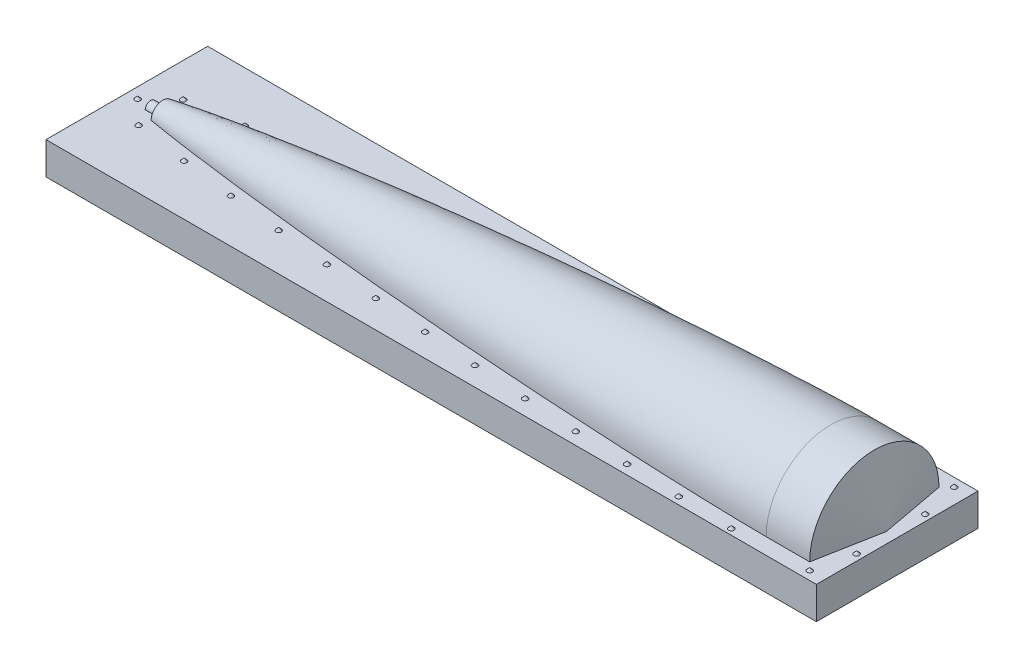
SolidWorks part; units mm, degrees
ref_plane "Front Plane" through (0, 0, 0) normal (0, 0, 1) x (1, 0, 0)
ref_plane "Top Plane" through (0, 0, 0) normal (0, 1, 0) x (1, 0, 0)
ref_plane "Right Plane" through (0, 0, 0) normal (1, 0, 0) x (0, 0, -1)
sketch "Sketch4" plane through (0, 0, 0) normal (0, 1, 0) x (1, 0, 0)
  line L0 (838.2216, 76.204) -> (889.568, 76.204)
  line L1 (889.568, 76.204) -> (903.7797, 0)
  line L2 (0, 0) -> (903.7797, 0) construction
  line L3 (49.2388, 6.35) -> (36.5388, 6.35)
  line L4 (49.2388, 6.35) -> (50.8212, 13.6952)
  line L5 (36.5388, 6.35) -> (33.9086, 0)
  line L6 (33.9086, 0) -> (903.7797, 0)
  spline S0 degree 4 poles (0.4116, 2.1681) (0.5035, 2.2183) (0.6887, 2.3156) (1.002, 2.4664) (1.4785, 2.6758) (2.1113, 2.9321) (3.0416, 3.2792) (4.4759, 3.768) (6.7944, 4.485) (9.7489, 5.3043) (13.1672, 6.1761) (17.4494, 7.1922) (22.1004, 8.2295) (27.2517, 9.3071) (32.654, 10.3833) (38.124, 11.4218) (42.9515, 12.3115) (49.1089, 13.4036) (53.3744, 14.1376) (58.7785, 15.0476) (63.6012, 15.8365) (68.9441, 16.698) (76.5361, 17.8884) (86.8586, 19.455) (98.7324, 21.1846) (110.6839, 22.8577) (120.8839, 24.2402) (131.1653, 25.6027) (141.4841, 26.9388) (153.5711, 28.4629) (167.4123, 30.1559) (181.2629, 31.8024) (195.1165, 33.4051) (212.4407, 35.3579) (229.7712, 37.247) (247.1084, 39.0777) (264.451, 40.854) (278.3284, 42.2438) (295.6787, 43.9433) (316.5048, 45.9247) (340.8095, 48.1557) (368.5956, 50.6005) (396.3905, 52.9447) (424.1933, 55.1916) (452.0037, 57.3435) (479.8212, 59.4019) (507.6453, 61.3674) (535.4759, 63.2399) (570.2718, 65.4634) (612.0388, 67.9402) (660.7836, 70.5395) (709.5475, 72.7531) (747.8743, 74.1952) (775.7546, 75.0554) (794.4539, 75.5468) (808.5625, 75.8548) (821.5655, 76.0752) (831.0831, 76.1755) (835.8421, 76.204) (838.2216, 76.204) knots 0 0 0 0 0 0.000497 0.000994 0.00165 0.002474 0.003736 0.005714 0.008837 0.014015 0.018266 0.022517 0.029658 0.0368 0.042975 0.04915 0.055325 0.061501 0.06978 0.07392 0.07806 0.08634 0.09462 0.110946 0.127272 0.143598 0.151761 0.159924 0.176484 0.193044 0.209604 0.226164 0.242723 0.259283 0.292403 0.308963 0.325522 0.342082 0.358642 0.391762 0.424881 0.458001 0.49112 0.52424 0.557359 0.590479 0.623599 0.656718 0.689838 0.756077 0.822316 0.888555 0.921675 0.938235 0.954794 0.977397 0.988699 1 1 1 1 1 construction
  spline S1 degree 4 poles (50.8212, 13.6952) (52.4334, 13.9739) (54.8422, 14.3848) (58.7785, 15.0476) (63.6012, 15.8365) (68.9441, 16.698) (76.5361, 17.8884) (86.8586, 19.455) (98.7324, 21.1846) (110.6839, 22.8577) (120.8839, 24.2402) (131.1653, 25.6027) (141.4841, 26.9388) (153.5711, 28.4629) (167.4123, 30.1559) (181.2629, 31.8024) (195.1165, 33.4051) (212.4407, 35.3579) (229.7712, 37.247) (247.1084, 39.0777) (264.451, 40.854) (278.3284, 42.2438) (295.6787, 43.9433) (316.5048, 45.9247) (340.8095, 48.1557) (368.5956, 50.6005) (396.3905, 52.9447) (424.1933, 55.1916) (452.0037, 57.3435) (479.8212, 59.4019) (507.6453, 61.3674) (535.4759, 63.2399) (570.2718, 65.4634) (612.0388, 67.9402) (660.7836, 70.5395) (709.5475, 72.7531) (747.8743, 74.1952) (775.7546, 75.0554) (794.4539, 75.5468) (808.5625, 75.8548) (821.5655, 76.0752) (831.0831, 76.1755) (835.8421, 76.204) (838.2216, 76.204) knots 0.061501 0.061501 0.061501 0.061501 0.061501 0.06978 0.07392 0.07806 0.08634 0.09462 0.110946 0.127272 0.143598 0.151761 0.159924 0.176484 0.193044 0.209604 0.226164 0.242723 0.259283 0.292403 0.308963 0.325522 0.342082 0.358642 0.391762 0.424881 0.458001 0.49112 0.52424 0.557359 0.590479 0.623599 0.656718 0.689838 0.756077 0.822316 0.888555 0.921675 0.938235 0.954794 0.977397 0.988699 1 1 1 1 1
  point P6 (0, 0)
  dimension "D1" = 869.8712
  dimension "D2" = 12.7
  dimension "D3" = 102.157
  dimension "D4" = 79.436
  dimension "D5" = 51.3464
  dimension "D6" = 76.204
revolve "Revolve1" add sketch "Sketch4" angle 180 about L2
sketch "Sketch5" plane through (0, 0, 0) normal (0, -1, 0) x (1, 0, 0)
  line L0 (8.5086, 95.254) -> (8.5086, -95.254)
  line L1 (889.568, -76.204) -> (838.2216, -76.204) construction
  line L2 (889.568, 76.204) -> (838.2216, 76.204) construction
  line L3 (8.5086, -95.254) -> (916.4797, -95.254)
  line L6 (8.5086, 95.254) -> (916.4797, 95.254)
  line L7 (916.4797, 95.254) -> (916.4797, -95.254)
  dimension "D1" = 12.7
  dimension "D2" = 19.05
  dimension "D3" = 19.05
  dimension "D4" = 25.4
extrude "Boss-Extrude1" add sketch "Sketch5" along normal blind 38.1
sketch "Sketch8" plane through (0, 0, 0) normal (0, 1, 0) x (1, 0, 0)
  line L0 (50.8212, -13.6952) -> (48.6578, -26.2096) construction
  line L1 (176.6029, -31.2441) -> (175.1098, -43.856) construction
  line L2 (302.896, -44.6243) -> (301.6912, -57.267) construction
  line L3 (429.4223, -55.5836) -> (428.429, -68.2447) construction
  line L4 (556.1056, -64.5474) -> (555.3063, -77.2222) construction
  line L5 (682.915, -71.5029) -> (682.3308, -84.1895) construction
  line L6 (809.8401, -75.8636) -> (809.5993, -88.5614) construction
  line L7 (896.6738, -38.102) -> (909.1586, -40.4303) construction
  line L8 (903.7797, 0) -> (889.568, -76.204) construction
  line L9 (889.568, -76.204) -> (898.5482, -85.1842) construction
  line L10 (889.568, -76.204) -> (838.2216, -76.204) construction
  line L11 (33.9086, 0) -> (21.2086, 0) construction
  line L12 (889.568, 76.204) -> (898.5482, 85.1842) construction
  line L13 (896.6738, 38.102) -> (909.1586, 40.4303) construction
  line L14 (809.8401, 75.8636) -> (809.5993, 88.5614) construction
  line L15 (682.915, 71.5029) -> (682.3308, 84.1895) construction
  line L16 (556.1056, 64.5474) -> (555.3063, 77.2222) construction
  line L17 (429.4223, 55.5836) -> (428.429, 68.2447) construction
  line L18 (302.896, 44.6243) -> (301.6912, 57.267) construction
  line L19 (176.6029, 31.2441) -> (175.1098, 43.856) construction
  line L20 (50.8212, 13.6952) -> (48.6578, 26.2096) construction
  line L21 (916.4797, 95.254) -> (916.4797, -95.254) construction
  line L22 (113.5986, -23.2471) -> (111.8762, -35.8298) construction
  line L23 (113.5986, 23.2471) -> (111.8762, 35.8298) construction
  line L24 (239.7108, -38.2899) -> (238.3781, -50.9198) construction
  line L25 (366.1358, -50.367) -> (365.0415, -63.0198) construction
  line L26 (492.7464, -60.3071) -> (491.85, -72.9754) construction
  line L27 (619.495, -68.2923) -> (618.7976, -80.9732) construction
  line L28 (746.3621, -74.0943) -> (745.9156, -86.7864) construction
  line L29 (746.3621, 74.0943) -> (745.9156, 86.7864) construction
  line L30 (619.495, 68.2923) -> (618.7976, 80.9732) construction
  line L31 (492.7464, 60.3071) -> (491.85, 72.9754) construction
  line L32 (366.1358, 50.367) -> (365.0415, 63.0198) construction
  line L33 (239.7108, 38.2899) -> (238.3781, 50.9198) construction
  line L61 (0, 0) -> (916.4797, 0) construction
  circle A0 centre (48.6578, -26.2096) radius 3.175
  circle A1 centre (175.1098, -43.856) radius 3.175
  circle A2 centre (301.6912, -57.267) radius 3.175
  circle A3 centre (428.429, -68.2447) radius 3.175
  circle A4 centre (555.3063, -77.2222) radius 3.175
  circle A5 centre (682.3308, -84.1895) radius 3.175
  circle A6 centre (809.5993, -88.5614) radius 3.175
  circle A7 centre (909.1586, -40.4303) radius 3.175
  circle A8 centre (898.5482, -85.1842) radius 3.175
  circle A9 centre (21.2086, 0) radius 3.175
  circle A10 centre (898.5482, 85.1842) radius 3.175
  circle A11 centre (909.1586, 40.4303) radius 3.175
  circle A12 centre (809.5993, 88.5614) radius 3.175
  circle A13 centre (682.3308, 84.1895) radius 3.175
  circle A14 centre (555.3063, 77.2222) radius 3.175
  circle A15 centre (428.429, 68.2447) radius 3.175
  circle A16 centre (301.6912, 57.267) radius 3.175
  circle A17 centre (175.1098, 43.856) radius 3.175
  circle A18 centre (48.6578, 26.2096) radius 3.175
  circle A19 centre (111.8762, -35.8298) radius 3.175
  circle A20 centre (111.8762, 35.8298) radius 3.175
  circle A21 centre (238.3781, -50.9198) radius 3.175
  circle A22 centre (365.0415, -63.0198) radius 3.175
  circle A23 centre (491.85, -72.9754) radius 3.175
  circle A24 centre (618.7976, -80.9732) radius 3.175
  circle A25 centre (745.9156, -86.7864) radius 3.175
  circle A26 centre (745.9156, 86.7864) radius 3.175
  circle A27 centre (618.7976, 80.9732) radius 3.175
  circle A28 centre (491.85, 72.9754) radius 3.175
  circle A29 centre (365.0415, 63.0198) radius 3.175
  circle A30 centre (238.3781, 50.9198) radius 3.175
  spline S3 degree 4 poles (838.2216, -76.204) (835.8421, -76.204) (831.0831, -76.1755) (821.5655, -76.0752) (808.5625, -75.8548) (794.4539, -75.5468) (775.7546, -75.0554) (747.8743, -74.1952) (709.5475, -72.7531) (660.7836, -70.5395) (612.0388, -67.9402) (570.2718, -65.4634) (535.4759, -63.2399) (507.6453, -61.3674) (479.8212, -59.4019) (452.0037, -57.3435) (424.1933, -55.1916) (396.3905, -52.9447) (368.5956, -50.6005) (340.8095, -48.1557) (316.5048, -45.9247) (295.6787, -43.9433) (278.3284, -42.2438) (264.451, -40.854) (247.1084, -39.0777) (229.7712, -37.247) (212.4407, -35.3579) (195.1165, -33.4051) (181.2629, -31.8024) (167.4123, -30.1559) (153.5711, -28.4629) (141.4841, -26.9388) (131.1653, -25.6027) (120.8839, -24.2402) (110.6839, -22.8577) (98.7324, -21.1846) (86.8586, -19.455) (76.5361, -17.8884) (68.9441, -16.698) (63.6012, -15.8365) (58.7785, -15.0476) (54.8422, -14.3848) (52.4334, -13.9739) (50.8212, -13.6952) knots 0.061501 0.061501 0.061501 0.061501 0.061501 0.072802 0.084103 0.106706 0.123266 0.139826 0.172945 0.239184 0.305424 0.371663 0.404782 0.437902 0.471022 0.504141 0.537261 0.57038 0.6035 0.636619 0.669739 0.702859 0.719418 0.735978 0.752538 0.769098 0.802217 0.818777 0.835337 0.851897 0.868456 0.885016 0.901576 0.909739 0.917902 0.934228 0.950554 0.96688 0.97516 0.98344 0.98758 0.99172 1 1 1 1 1 construction
  dimension "D1" = 12.7
  dimension "D2" = 6.35
  dimension "D4" = 127
  dimension "D7" = 63.5
  dimension "D10" = 63.5
  dimension "D13" = 63.5
  dimension "D9" = 63.5
  dimension "D3" = 127
  dimension "D5" = 127
  dimension "D6" = 135
  dimension "D8" = 127
  dimension "D11" = 127
  dimension "D12" = 63.5
  dimension "D14" = 127
  dimension "D15" = 63.5
extrude "Boss-Extrude3" add sketch "Sketch8" along normal blind 6.35 draft 45
draft "Draft3" [suppressed] type of draft neutral plane draft angle 45 faces to draft 18 parameters "D1"=45
